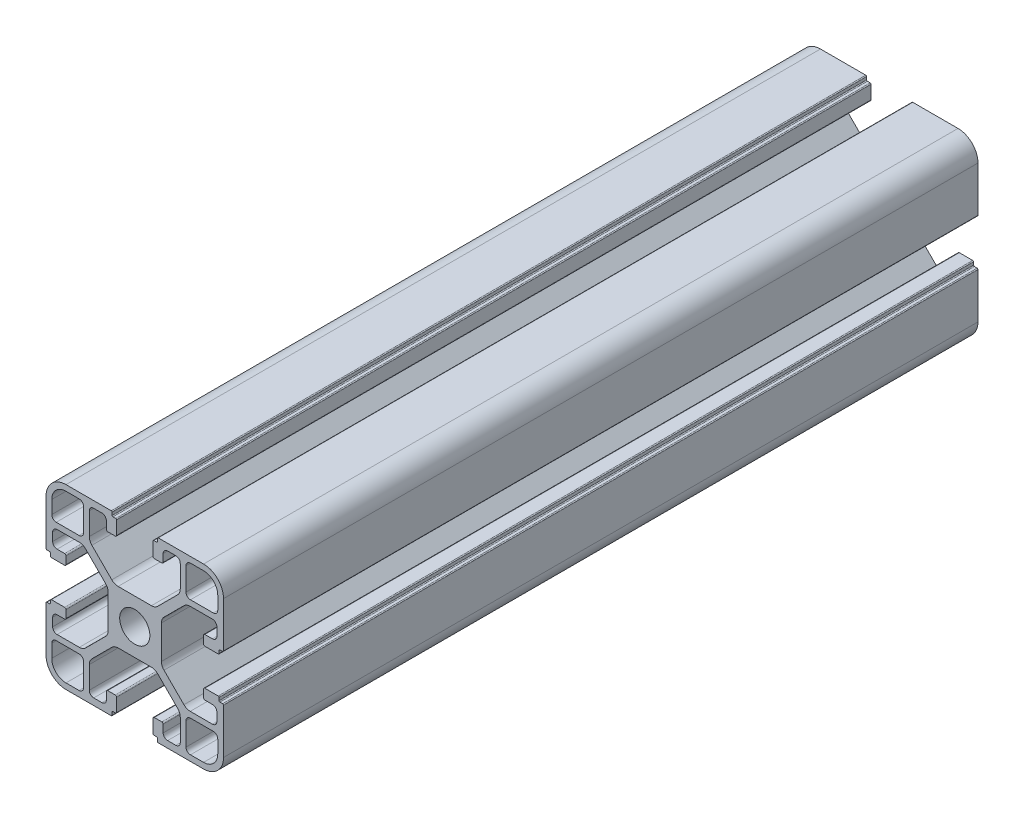
SolidWorks part; units mm, degrees
material "6063-T5"
ref_plane "Front Plane" through (0, 0, 0) normal (0, 0, 1) x (1, 0, 0)
ref_plane "Top Plane" through (0, 0, 0) normal (0, 1, 0) x (1, 0, 0)
ref_plane "Right Plane" through (0, 0, 0) normal (1, 0, 0) x (0, 0, -1)
sketch "Sketch2" plane through (0, 0, 0) normal (0, 0, 1) x (1, 0, 0)
  line L0 (4.5, 0) -> (14.7, 0)
  line L1 (40, 4.5) -> (40, 14.7)
  line L2 (35.5, 40) -> (25.3, 40)
  line L3 (0, 35.5) -> (0, 25.3)
  line L4 (15.9, 1.2) -> (15.9, 4.2)
  line L5 (24.1, 1.2) -> (24.1, 4.2)
  line L6 (38.8, 24.1) -> (35.8, 24.1)
  line L7 (35.5, 24.4) -> (35.5, 26.1)
  line L8 (14, 23.7574) -> (14, 16.2426)
  line L9 (16.2426, 14) -> (23.7574, 14)
  line L10 (26, 16.2426) -> (26, 23.7574)
  line L11 (13.4142, 14.8284) -> (8.9216, 10.3358)
  line L12 (23.7574, 26) -> (16.2426, 26)
  line L13 (4.5, 24.4) -> (4.5, 26.1)
  line L14 (1.2, 24.1) -> (4.2, 24.1)
  line L15 (15.9, 38.8) -> (15.9, 35.8)
  line L16 (14.8284, 26.5858) -> (10.3358, 31.0784)
  line L17 (13.4142, 25.1716) -> (8.9216, 29.6642)
  line L18 (14.8284, 13.4142) -> (10.3358, 8.9216)
  line L19 (25.1716, 13.4142) -> (29.6642, 8.9216)
  line L20 (26.5858, 14.8284) -> (31.0784, 10.3358)
  line L21 (26.5858, 25.1716) -> (31.0784, 29.6642)
  line L22 (25.1716, 26.5858) -> (29.6642, 31.0784)
  line L23 (24.1, 38.8) -> (24.1, 35.8)
  line L24 (14.7, 40) -> (4.5, 40)
  line L25 (25.3, 0) -> (35.5, 0)
  line L26 (38.8, 15.9) -> (35.8, 15.9)
  line L27 (40, 25.3) -> (40, 35.5)
  line L28 (1.2, 15.9) -> (4.2, 15.9)
  line L29 (0, 14.7) -> (0, 4.5)
  line L30 (4.5, 15.6) -> (4.5, 13.9)
  line L31 (35.5, 15.6) -> (35.5, 13.9)
  line L32 (15.6, 35.5) -> (13.9, 35.5)
  line L33 (24.4, 35.5) -> (26.1, 35.5)
  line L34 (15.6, 4.5) -> (13.9, 4.5)
  line L35 (24.4, 4.5) -> (26.1, 4.5)
  line L36 (12.6, 38.5) -> (10.75, 38.5)
  line L37 (1.5, 12.6) -> (1.5, 10.75)
  line L38 (27.4, 1.5) -> (29.25, 1.5)
  line L39 (38.5, 27.4) -> (38.5, 29.25)
  line L40 (38.5, 10.75) -> (38.5, 12.6)
  line L41 (29.25, 38.5) -> (27.4, 38.5)
  line L42 (1.5, 29.25) -> (1.5, 27.4)
  line L43 (10.75, 1.5) -> (12.6, 1.5)
  line L44 (35.8, 26.4) -> (37.5, 26.4)
  line L45 (35.8, 13.6) -> (37.5, 13.6)
  line L46 (4.2, 26.4) -> (2.5, 26.4)
  line L47 (13.6, 35.8) -> (13.6, 37.5)
  line L48 (26.4, 35.8) -> (26.4, 37.5)
  line L49 (4.2, 13.6) -> (2.5, 13.6)
  line L50 (13.6, 4.2) -> (13.6, 2.5)
  line L51 (26.4, 4.2) -> (26.4, 2.5)
  line L52 (9.75, 7.5074) -> (9.75, 2.5)
  line L53 (30.25, 7.5074) -> (30.25, 2.5)
  line L54 (9.75, 37.5) -> (9.75, 32.4926)
  line L55 (30.25, 37.5) -> (30.25, 32.4926)
  line L56 (32.4926, 30.25) -> (37.5, 30.25)
  line L57 (37.5, 9.75) -> (32.4926, 9.75)
  line L58 (2.5, 30.25) -> (7.5074, 30.25)
  line L59 (2.5, 9.75) -> (7.5074, 9.75)
  line L60 (31.55, 37.7) -> (31.55, 32.55)
  line L61 (32.55, 31.55) -> (37.7, 31.55)
  line L62 (1.3, 35.5) -> (1.3, 32.55)
  line L63 (4.5, 38.7) -> (7.45, 38.7)
  line L64 (32.55, 38.7) -> (35.5, 38.7)
  line L65 (38.7, 35.5) -> (38.7, 32.55)
  line L66 (8.45, 37.7) -> (8.45, 32.55)
  line L67 (2.3, 31.55) -> (7.45, 31.55)
  line L68 (1.3, 7.45) -> (1.3, 4.5)
  line L69 (2.3, 8.45) -> (7.45, 8.45)
  line L70 (8.45, 7.45) -> (8.45, 2.3)
  line L71 (4.5, 1.3) -> (7.45, 1.3)
  line L72 (31.55, 7.45) -> (31.55, 2.3)
  line L73 (32.55, 8.45) -> (37.7, 8.45)
  line L74 (38.7, 7.45) -> (38.7, 4.5)
  line L75 (32.55, 1.3) -> (35.5, 1.3)
  line L77 (14.9, 39.8) -> (14.9, 39.2)
  line L78 (15.1, 39) -> (15.7, 39)
  line L79 (25.1, 39.8) -> (25.1, 39.2)
  line L80 (24.9, 39) -> (24.3, 39)
  line L81 (25.1, 0.2) -> (25.1, 0.8)
  line L82 (24.9, 1) -> (24.3, 1)
  line L83 (14.9, 0.2) -> (14.9, 0.8)
  line L84 (15.1, 1) -> (15.7, 1)
  line L85 (0.2, 25.1) -> (0.8, 25.1)
  line L86 (1, 24.9) -> (1, 24.3)
  line L87 (0.2, 14.9) -> (0.8, 14.9)
  line L88 (1, 15.1) -> (1, 15.7)
  line L89 (39.8, 25.1) -> (39.2, 25.1)
  line L90 (39, 24.9) -> (39, 24.3)
  line L91 (39, 15.7) -> (39, 15.1)
  line L92 (39.2, 14.9) -> (39.8, 14.9)
  circle A0 centre (20, 20) radius 3.4
  arc A1 (1.3, 35.5) -> (4.5, 38.7) centre (4.5, 35.5) cw
  arc A2 (1.3, 4.5) -> (4.5, 1.3) centre (4.5, 4.5) ccw
  arc A3 (38.7, 4.5) -> (35.5, 1.3) centre (35.5, 4.5) cw
  arc A4 (35.5, 38.7) -> (38.7, 35.5) centre (35.5, 35.5) cw
  arc A5 (40, 35.5) -> (35.5, 40) centre (35.5, 35.5) ccw
  arc A6 (35.5, 0) -> (40, 4.5) centre (35.5, 4.5) ccw
  arc A7 (4.5, 0) -> (0, 4.5) centre (4.5, 4.5) cw
  arc A8 (4.5, 40) -> (0, 35.5) centre (4.5, 35.5) ccw
  arc A9 (13.4142, 14.8284) -> (14, 16.2426) centre (12, 16.2426) ccw
  arc A10 (7.5074, 9.75) -> (8.9216, 10.3358) centre (7.5074, 11.75) ccw
  arc A11 (9.75, 7.5074) -> (10.3358, 8.9216) centre (11.75, 7.5074) cw
  arc A12 (30.25, 7.5074) -> (29.6642, 8.9216) centre (28.25, 7.5074) ccw
  arc A13 (14.8284, 13.4142) -> (16.2426, 14) centre (16.2426, 12) cw
  arc A14 (25.1716, 13.4142) -> (23.7574, 14) centre (23.7574, 12) ccw
  arc A15 (32.4926, 9.75) -> (31.0784, 10.3358) centre (32.4926, 11.75) cw
  arc A16 (26.5858, 14.8284) -> (26, 16.2426) centre (28, 16.2426) cw
  arc A17 (32.4926, 30.25) -> (31.0784, 29.6642) centre (32.4926, 28.25) ccw
  arc A18 (26.5858, 25.1716) -> (26, 23.7574) centre (28, 23.7574) ccw
  arc A19 (13.4142, 25.1716) -> (14, 23.7574) centre (12, 23.7574) cw
  arc A20 (7.5074, 30.25) -> (8.9216, 29.6642) centre (7.5074, 28.25) cw
  arc A21 (9.75, 32.4926) -> (10.3358, 31.0784) centre (11.75, 32.4926) ccw
  arc A22 (30.25, 32.4926) -> (29.6642, 31.0784) centre (28.25, 32.4926) cw
  arc A23 (25.1716, 26.5858) -> (23.7574, 26) centre (23.7574, 28) cw
  arc A24 (14.8284, 26.5858) -> (16.2426, 26) centre (16.2426, 28) ccw
  arc A25 (37.7, 8.45) -> (38.7, 7.45) centre (37.7, 7.45) cw
  arc A26 (31.55, 2.3) -> (32.55, 1.3) centre (32.55, 2.3) ccw
  arc A27 (31.55, 7.45) -> (32.55, 8.45) centre (32.55, 7.45) cw
  arc A28 (8.45, 2.3) -> (7.45, 1.3) centre (7.45, 2.3) cw
  arc A29 (1.3, 7.45) -> (2.3, 8.45) centre (2.3, 7.45) cw
  arc A30 (7.45, 8.45) -> (8.45, 7.45) centre (7.45, 7.45) cw
  arc A31 (38.7, 32.55) -> (37.7, 31.55) centre (37.7, 32.55) cw
  arc A32 (31.55, 32.55) -> (32.55, 31.55) centre (32.55, 32.55) ccw
  arc A33 (31.55, 37.7) -> (32.55, 38.7) centre (32.55, 37.7) cw
  arc A34 (7.45, 38.7) -> (8.45, 37.7) centre (7.45, 37.7) cw
  arc A35 (8.45, 32.55) -> (7.45, 31.55) centre (7.45, 32.55) cw
  arc A36 (1.3, 32.55) -> (2.3, 31.55) centre (2.3, 32.55) ccw
  arc A37 (30.25, 2.5) -> (29.25, 1.5) centre (29.25, 2.5) cw
  arc A38 (26.4, 2.5) -> (27.4, 1.5) centre (27.4, 2.5) ccw
  arc A39 (13.6, 2.5) -> (12.6, 1.5) centre (12.6, 2.5) cw
  arc A40 (9.75, 2.5) -> (10.75, 1.5) centre (10.75, 2.5) ccw
  arc A41 (26.4, 37.5) -> (27.4, 38.5) centre (27.4, 37.5) cw
  arc A42 (30.25, 37.5) -> (29.25, 38.5) centre (29.25, 37.5) ccw
  arc A43 (37.5, 26.4) -> (38.5, 27.4) centre (37.5, 27.4) ccw
  arc A44 (37.5, 30.25) -> (38.5, 29.25) centre (37.5, 29.25) cw
  arc A45 (37.5, 13.6) -> (38.5, 12.6) centre (37.5, 12.6) cw
  arc A46 (37.5, 9.75) -> (38.5, 10.75) centre (37.5, 10.75) ccw
  arc A47 (2.5, 9.75) -> (1.5, 10.75) centre (2.5, 10.75) cw
  arc A48 (2.5, 13.6) -> (1.5, 12.6) centre (2.5, 12.6) ccw
  arc A49 (2.5, 26.4) -> (1.5, 27.4) centre (2.5, 27.4) cw
  arc A50 (2.5, 30.25) -> (1.5, 29.25) centre (2.5, 29.25) ccw
  arc A51 (9.75, 37.5) -> (10.75, 38.5) centre (10.75, 37.5) cw
  arc A52 (13.6, 37.5) -> (12.6, 38.5) centre (12.6, 37.5) ccw
  arc A53 (26.1, 35.5) -> (26.4, 35.8) centre (26.1, 35.8) ccw
  arc A54 (24.1, 35.8) -> (24.4, 35.5) centre (24.4, 35.8) ccw
  arc A55 (15.9, 35.8) -> (15.6, 35.5) centre (15.6, 35.8) cw
  arc A56 (13.9, 35.5) -> (13.6, 35.8) centre (13.9, 35.8) cw
  arc A57 (13.9, 4.5) -> (13.6, 4.2) centre (13.9, 4.2) ccw
  arc A58 (15.9, 4.2) -> (15.6, 4.5) centre (15.6, 4.2) ccw
  arc A59 (24.1, 4.2) -> (24.4, 4.5) centre (24.4, 4.2) cw
  arc A60 (26.1, 4.5) -> (26.4, 4.2) centre (26.1, 4.2) cw
  arc A61 (35.5, 13.9) -> (35.8, 13.6) centre (35.8, 13.9) ccw
  arc A62 (35.8, 15.9) -> (35.5, 15.6) centre (35.8, 15.6) ccw
  arc A63 (35.8, 24.1) -> (35.5, 24.4) centre (35.8, 24.4) cw
  arc A64 (35.5, 26.1) -> (35.8, 26.4) centre (35.8, 26.1) cw
  arc A65 (4.5, 13.9) -> (4.2, 13.6) centre (4.2, 13.9) cw
  arc A66 (4.2, 15.9) -> (4.5, 15.6) centre (4.2, 15.6) cw
  arc A67 (4.2, 24.1) -> (4.5, 24.4) centre (4.2, 24.4) ccw
  arc A68 (4.5, 26.1) -> (4.2, 26.4) centre (4.2, 26.1) ccw
  arc A69 (25.3, 0) -> (25.1, 0.2) centre (25.3, 0.2) cw
  arc A70 (25.1, 0.8) -> (24.9, 1) centre (24.9, 0.8) ccw
  arc A71 (24.3, 1) -> (24.1, 1.2) centre (24.3, 1.2) cw
  arc A72 (14.7, 0) -> (14.9, 0.2) centre (14.7, 0.2) ccw
  arc A73 (14.9, 0.8) -> (15.1, 1) centre (15.1, 0.8) cw
  arc A74 (15.7, 1) -> (15.9, 1.2) centre (15.7, 1.2) ccw
  arc A75 (39.8, 14.9) -> (40, 14.7) centre (39.8, 14.7) cw
  arc A76 (39, 15.1) -> (39.2, 14.9) centre (39.2, 15.1) ccw
  arc A77 (38.8, 15.9) -> (39, 15.7) centre (38.8, 15.7) cw
  arc A78 (0, 25.3) -> (0.2, 25.1) centre (0.2, 25.3) ccw
  arc A79 (0.8, 25.1) -> (1, 24.9) centre (0.8, 24.9) cw
  arc A80 (1, 24.3) -> (1.2, 24.1) centre (1.2, 24.3) ccw
  arc A81 (0, 14.7) -> (0.2, 14.9) centre (0.2, 14.7) cw
  arc A82 (0.8, 14.9) -> (1, 15.1) centre (0.8, 15.1) ccw
  arc A83 (1, 15.7) -> (1.2, 15.9) centre (1.2, 15.7) cw
  arc A84 (39, 24.3) -> (38.8, 24.1) centre (38.8, 24.3) cw
  arc A85 (39.2, 25.1) -> (39, 24.9) centre (39.2, 24.9) ccw
  arc A86 (40, 25.3) -> (39.8, 25.1) centre (39.8, 25.3) cw
  arc A87 (24.3, 39) -> (24.1, 38.8) centre (24.3, 38.8) ccw
  arc A88 (25.1, 39.2) -> (24.9, 39) centre (24.9, 39.2) cw
  arc A89 (25.3, 40) -> (25.1, 39.8) centre (25.3, 39.8) ccw
  arc A90 (14.9, 39.2) -> (15.1, 39) centre (15.1, 39.2) ccw
  arc A91 (15.7, 39) -> (15.9, 38.8) centre (15.7, 38.8) cw
  arc A92 (14.7, 40) -> (14.9, 39.8) centre (14.7, 39.8) cw
  point P93 (0, 0)
extrude "Boss-Extrude1" add sketch "Sketch2" along normal blind 170
sketch "Sketch3" plane through (0, 0, 170) normal (0, 0, 1) x (1, 0, 0)
  line L76 (25.3, 0) -> (35.5, 0)
  line L77 (40, 4.5) -> (40, 14.7)
  line L78 (39.8, 14.9) -> (39.2, 14.9)
  line L79 (39, 15.1) -> (39, 15.7)
  line L80 (38.8, 15.9) -> (35.8, 15.9)
  line L81 (35.5, 15.6) -> (35.5, 13.9)
  line L82 (35.8, 13.6) -> (37.5, 13.6)
  line L83 (38.5, 12.6) -> (38.5, 10.75)
  line L84 (37.5, 9.75) -> (32.4926, 9.75)
  line L85 (31.0784, 10.3358) -> (26.5858, 14.8284)
  line L86 (26, 16.2426) -> (26, 23.7574)
  line L87 (26.5858, 25.1716) -> (31.0784, 29.6642)
  line L88 (32.4926, 30.25) -> (37.5, 30.25)
  line L89 (38.5, 29.25) -> (38.5, 27.4)
  line L90 (37.5, 26.4) -> (35.8, 26.4)
  line L91 (35.5, 26.1) -> (35.5, 24.4)
  line L92 (35.8, 24.1) -> (38.8, 24.1)
  line L93 (39, 24.3) -> (39, 24.9)
  line L94 (39.2, 25.1) -> (39.8, 25.1)
  line L95 (40, 25.3) -> (40, 35.5)
  line L96 (35.5, 40) -> (25.3, 40)
  line L97 (25.1, 39.8) -> (25.1, 39.2)
  line L98 (24.9, 39) -> (24.3, 39)
  line L99 (24.1, 38.8) -> (24.1, 35.8)
  line L100 (24.4, 35.5) -> (26.1, 35.5)
  line L101 (26.4, 35.8) -> (26.4, 37.5)
  line L102 (27.4, 38.5) -> (29.25, 38.5)
  line L103 (30.25, 37.5) -> (30.25, 32.4926)
  line L104 (29.6642, 31.0784) -> (25.1716, 26.5858)
  line L105 (23.7574, 26) -> (16.2426, 26)
  line L106 (14.8284, 26.5858) -> (10.3358, 31.0784)
  line L107 (9.75, 32.4926) -> (9.75, 37.5)
  line L108 (10.75, 38.5) -> (12.6, 38.5)
  line L109 (13.6, 37.5) -> (13.6, 35.8)
  line L110 (13.9, 35.5) -> (15.6, 35.5)
  line L111 (15.9, 35.8) -> (15.9, 38.8)
  line L112 (15.7, 39) -> (15.1, 39)
  line L113 (14.9, 39.2) -> (14.9, 39.8)
  line L114 (14.7, 40) -> (4.5, 40)
  line L115 (0, 35.5) -> (0, 25.3)
  line L116 (0.2, 25.1) -> (0.8, 25.1)
  line L117 (1, 24.9) -> (1, 24.3)
  line L118 (1.2, 24.1) -> (4.2, 24.1)
  line L119 (4.5, 24.4) -> (4.5, 26.1)
  line L120 (4.2, 26.4) -> (2.5, 26.4)
  line L121 (1.5, 27.4) -> (1.5, 29.25)
  line L122 (2.5, 30.25) -> (7.5074, 30.25)
  line L123 (8.9216, 29.6642) -> (13.4142, 25.1716)
  line L124 (14, 23.7574) -> (14, 16.2426)
  line L125 (13.4142, 14.8284) -> (8.9216, 10.3358)
  line L126 (7.5074, 9.75) -> (2.5, 9.75)
  line L127 (1.5, 10.75) -> (1.5, 12.6)
  line L128 (2.5, 13.6) -> (4.2, 13.6)
  line L129 (4.5, 13.9) -> (4.5, 15.6)
  line L130 (4.2, 15.9) -> (1.2, 15.9)
  line L131 (1, 15.7) -> (1, 15.1)
  line L132 (0.8, 14.9) -> (0.2, 14.9)
  line L133 (0, 14.7) -> (0, 4.5)
  line L134 (4.5, 0) -> (14.7, 0)
  line L135 (14.9, 0.2) -> (14.9, 0.8)
  line L136 (15.1, 1) -> (15.7, 1)
  line L137 (15.9, 1.2) -> (15.9, 4.2)
  line L138 (15.6, 4.5) -> (13.9, 4.5)
  line L139 (13.6, 4.2) -> (13.6, 2.5)
  line L140 (12.6, 1.5) -> (10.75, 1.5)
  line L141 (9.75, 2.5) -> (9.75, 7.5074)
  line L142 (10.3358, 8.9216) -> (14.8284, 13.4142)
  line L143 (16.2426, 14) -> (23.7574, 14)
  line L144 (25.1716, 13.4142) -> (29.6642, 8.9216)
  line L145 (30.25, 7.5074) -> (30.25, 2.5)
  line L146 (29.25, 1.5) -> (27.4, 1.5)
  line L147 (26.4, 2.5) -> (26.4, 4.2)
  line L148 (26.1, 4.5) -> (24.4, 4.5)
  line L149 (24.1, 4.2) -> (24.1, 1.2)
  line L150 (24.3, 1) -> (24.9, 1)
  line L151 (25.1, 0.8) -> (25.1, 0.2)
  line L152 (25.3, 0) -> (35.5, 0)
  line L153 (40, 4.5) -> (40, 14.7)
  line L154 (39.8, 14.9) -> (39.2, 14.9)
  line L155 (39, 15.1) -> (39, 15.7)
  line L156 (38.8, 15.9) -> (35.8, 15.9)
  line L157 (35.5, 15.6) -> (35.5, 13.9)
  line L158 (35.8, 13.6) -> (37.5, 13.6)
  line L159 (38.5, 12.6) -> (38.5, 10.75)
  line L160 (37.5, 9.75) -> (32.4926, 9.75)
  line L161 (31.0784, 10.3358) -> (26.5858, 14.8284)
  line L162 (26, 16.2426) -> (26, 23.7574)
  line L163 (26.5858, 25.1716) -> (31.0784, 29.6642)
  line L164 (32.4926, 30.25) -> (37.5, 30.25)
  line L165 (38.5, 29.25) -> (38.5, 27.4)
  line L166 (37.5, 26.4) -> (35.8, 26.4)
  line L167 (35.5, 26.1) -> (35.5, 24.4)
  line L168 (35.8, 24.1) -> (38.8, 24.1)
  line L169 (39, 24.3) -> (39, 24.9)
  line L170 (39.2, 25.1) -> (39.8, 25.1)
  line L171 (40, 25.3) -> (40, 35.5)
  line L172 (35.5, 40) -> (25.3, 40)
  line L173 (25.1, 39.8) -> (25.1, 39.2)
  line L174 (24.9, 39) -> (24.3, 39)
  line L175 (24.1, 38.8) -> (24.1, 35.8)
  line L176 (24.4, 35.5) -> (26.1, 35.5)
  line L177 (26.4, 35.8) -> (26.4, 37.5)
  line L178 (27.4, 38.5) -> (29.25, 38.5)
  line L179 (30.25, 37.5) -> (30.25, 32.4926)
  line L180 (29.6642, 31.0784) -> (25.1716, 26.5858)
  line L181 (23.7574, 26) -> (16.2426, 26)
  line L182 (14.8284, 26.5858) -> (10.3358, 31.0784)
  line L183 (9.75, 32.4926) -> (9.75, 37.5)
  line L184 (10.75, 38.5) -> (12.6, 38.5)
  line L185 (13.6, 37.5) -> (13.6, 35.8)
  line L186 (13.9, 35.5) -> (15.6, 35.5)
  line L187 (15.9, 35.8) -> (15.9, 38.8)
  line L188 (15.7, 39) -> (15.1, 39)
  line L189 (14.9, 39.2) -> (14.9, 39.8)
  line L190 (14.7, 40) -> (4.5, 40)
  line L191 (0, 35.5) -> (0, 25.3)
  line L192 (0.2, 25.1) -> (0.8, 25.1)
  line L193 (1, 24.9) -> (1, 24.3)
  line L194 (1.2, 24.1) -> (4.2, 24.1)
  line L195 (4.5, 24.4) -> (4.5, 26.1)
  line L196 (4.2, 26.4) -> (2.5, 26.4)
  line L197 (1.5, 27.4) -> (1.5, 29.25)
  line L198 (2.5, 30.25) -> (7.5074, 30.25)
  line L199 (8.9216, 29.6642) -> (13.4142, 25.1716)
  line L200 (14, 23.7574) -> (14, 16.2426)
  line L201 (13.4142, 14.8284) -> (8.9216, 10.3358)
  line L202 (7.5074, 9.75) -> (2.5, 9.75)
  line L203 (1.5, 10.75) -> (1.5, 12.6)
  line L204 (2.5, 13.6) -> (4.2, 13.6)
  line L205 (4.5, 13.9) -> (4.5, 15.6)
  line L206 (4.2, 15.9) -> (1.2, 15.9)
  line L207 (1, 15.7) -> (1, 15.1)
  line L208 (0.8, 14.9) -> (0.2, 14.9)
  line L209 (0, 14.7) -> (0, 4.5)
  line L210 (4.5, 0) -> (14.7, 0)
  line L211 (14.9, 0.2) -> (14.9, 0.8)
  line L212 (15.1, 1) -> (15.7, 1)
  line L213 (15.9, 1.2) -> (15.9, 4.2)
  line L214 (15.6, 4.5) -> (13.9, 4.5)
  line L215 (13.6, 4.2) -> (13.6, 2.5)
  line L216 (12.6, 1.5) -> (10.75, 1.5)
  line L217 (9.75, 2.5) -> (9.75, 7.5074)
  line L218 (10.3358, 8.9216) -> (14.8284, 13.4142)
  line L219 (16.2426, 14) -> (23.7574, 14)
  line L220 (25.1716, 13.4142) -> (29.6642, 8.9216)
  line L221 (30.25, 7.5074) -> (30.25, 2.5)
  line L222 (29.25, 1.5) -> (27.4, 1.5)
  line L223 (26.4, 2.5) -> (26.4, 4.2)
  line L224 (26.1, 4.5) -> (24.4, 4.5)
  line L225 (24.1, 4.2) -> (24.1, 1.2)
  line L226 (24.3, 1) -> (24.9, 1)
  line L227 (25.1, 0.8) -> (25.1, 0.2)
  arc A76 (25.1, 0.2) -> (25.3, 0) centre (25.3, 0.2) ccw
  arc A77 (35.5, 0) -> (40, 4.5) centre (35.5, 4.5) ccw
  arc A78 (40, 14.7) -> (39.8, 14.9) centre (39.8, 14.7) ccw
  arc A79 (39, 15.1) -> (39.2, 14.9) centre (39.2, 15.1) ccw
  arc A80 (39, 15.7) -> (38.8, 15.9) centre (38.8, 15.7) ccw
  arc A81 (35.8, 15.9) -> (35.5, 15.6) centre (35.8, 15.6) ccw
  arc A82 (35.5, 13.9) -> (35.8, 13.6) centre (35.8, 13.9) ccw
  arc A83 (38.5, 12.6) -> (37.5, 13.6) centre (37.5, 12.6) ccw
  arc A84 (37.5, 9.75) -> (38.5, 10.75) centre (37.5, 10.75) ccw
  arc A85 (31.0784, 10.3358) -> (32.4926, 9.75) centre (32.4926, 11.75) ccw
  arc A86 (26, 16.2426) -> (26.5858, 14.8284) centre (28, 16.2426) ccw
  arc A87 (26.5858, 25.1716) -> (26, 23.7574) centre (28, 23.7574) ccw
  arc A88 (32.4926, 30.25) -> (31.0784, 29.6642) centre (32.4926, 28.25) ccw
  arc A89 (38.5, 29.25) -> (37.5, 30.25) centre (37.5, 29.25) ccw
  arc A90 (37.5, 26.4) -> (38.5, 27.4) centre (37.5, 27.4) ccw
  arc A91 (35.8, 26.4) -> (35.5, 26.1) centre (35.8, 26.1) ccw
  arc A92 (35.5, 24.4) -> (35.8, 24.1) centre (35.8, 24.4) ccw
  arc A93 (38.8, 24.1) -> (39, 24.3) centre (38.8, 24.3) ccw
  arc A94 (39.2, 25.1) -> (39, 24.9) centre (39.2, 24.9) ccw
  arc A95 (39.8, 25.1) -> (40, 25.3) centre (39.8, 25.3) ccw
  arc A96 (40, 35.5) -> (35.5, 40) centre (35.5, 35.5) ccw
  arc A97 (25.3, 40) -> (25.1, 39.8) centre (25.3, 39.8) ccw
  arc A98 (24.9, 39) -> (25.1, 39.2) centre (24.9, 39.2) ccw
  arc A99 (24.3, 39) -> (24.1, 38.8) centre (24.3, 38.8) ccw
  arc A100 (24.1, 35.8) -> (24.4, 35.5) centre (24.4, 35.8) ccw
  arc A101 (26.1, 35.5) -> (26.4, 35.8) centre (26.1, 35.8) ccw
  arc A102 (27.4, 38.5) -> (26.4, 37.5) centre (27.4, 37.5) ccw
  arc A103 (30.25, 37.5) -> (29.25, 38.5) centre (29.25, 37.5) ccw
  arc A104 (29.6642, 31.0784) -> (30.25, 32.4926) centre (28.25, 32.4926) ccw
  arc A105 (23.7574, 26) -> (25.1716, 26.5858) centre (23.7574, 28) ccw
  arc A106 (14.8284, 26.5858) -> (16.2426, 26) centre (16.2426, 28) ccw
  arc A107 (9.75, 32.4926) -> (10.3358, 31.0784) centre (11.75, 32.4926) ccw
  arc A108 (10.75, 38.5) -> (9.75, 37.5) centre (10.75, 37.5) ccw
  arc A109 (13.6, 37.5) -> (12.6, 38.5) centre (12.6, 37.5) ccw
  arc A110 (13.6, 35.8) -> (13.9, 35.5) centre (13.9, 35.8) ccw
  arc A111 (15.6, 35.5) -> (15.9, 35.8) centre (15.6, 35.8) ccw
  arc A112 (15.9, 38.8) -> (15.7, 39) centre (15.7, 38.8) ccw
  arc A113 (14.9, 39.2) -> (15.1, 39) centre (15.1, 39.2) ccw
  arc A114 (14.9, 39.8) -> (14.7, 40) centre (14.7, 39.8) ccw
  arc A115 (4.5, 40) -> (0, 35.5) centre (4.5, 35.5) ccw
  arc A116 (0, 25.3) -> (0.2, 25.1) centre (0.2, 25.3) ccw
  arc A117 (1, 24.9) -> (0.8, 25.1) centre (0.8, 24.9) ccw
  arc A118 (1, 24.3) -> (1.2, 24.1) centre (1.2, 24.3) ccw
  arc A119 (4.2, 24.1) -> (4.5, 24.4) centre (4.2, 24.4) ccw
  arc A120 (4.5, 26.1) -> (4.2, 26.4) centre (4.2, 26.1) ccw
  arc A121 (1.5, 27.4) -> (2.5, 26.4) centre (2.5, 27.4) ccw
  arc A122 (2.5, 30.25) -> (1.5, 29.25) centre (2.5, 29.25) ccw
  arc A123 (8.9216, 29.6642) -> (7.5074, 30.25) centre (7.5074, 28.25) ccw
  arc A124 (14, 23.7574) -> (13.4142, 25.1716) centre (12, 23.7574) ccw
  arc A125 (13.4142, 14.8284) -> (14, 16.2426) centre (12, 16.2426) ccw
  arc A126 (7.5074, 9.75) -> (8.9216, 10.3358) centre (7.5074, 11.75) ccw
  arc A127 (1.5, 10.75) -> (2.5, 9.75) centre (2.5, 10.75) ccw
  arc A128 (2.5, 13.6) -> (1.5, 12.6) centre (2.5, 12.6) ccw
  arc A129 (4.2, 13.6) -> (4.5, 13.9) centre (4.2, 13.9) ccw
  arc A130 (4.5, 15.6) -> (4.2, 15.9) centre (4.2, 15.6) ccw
  arc A131 (1.2, 15.9) -> (1, 15.7) centre (1.2, 15.7) ccw
  arc A132 (0.8, 14.9) -> (1, 15.1) centre (0.8, 15.1) ccw
  arc A133 (0.2, 14.9) -> (0, 14.7) centre (0.2, 14.7) ccw
  arc A134 (0, 4.5) -> (4.5, 0) centre (4.5, 4.5) ccw
  arc A135 (14.7, 0) -> (14.9, 0.2) centre (14.7, 0.2) ccw
  arc A136 (15.1, 1) -> (14.9, 0.8) centre (15.1, 0.8) ccw
  arc A137 (15.7, 1) -> (15.9, 1.2) centre (15.7, 1.2) ccw
  arc A138 (15.9, 4.2) -> (15.6, 4.5) centre (15.6, 4.2) ccw
  arc A139 (13.9, 4.5) -> (13.6, 4.2) centre (13.9, 4.2) ccw
  arc A140 (12.6, 1.5) -> (13.6, 2.5) centre (12.6, 2.5) ccw
  arc A141 (9.75, 2.5) -> (10.75, 1.5) centre (10.75, 2.5) ccw
  arc A142 (10.3358, 8.9216) -> (9.75, 7.5074) centre (11.75, 7.5074) ccw
  arc A143 (16.2426, 14) -> (14.8284, 13.4142) centre (16.2426, 12) ccw
  arc A144 (25.1716, 13.4142) -> (23.7574, 14) centre (23.7574, 12) ccw
  arc A145 (30.25, 7.5074) -> (29.6642, 8.9216) centre (28.25, 7.5074) ccw
  arc A146 (29.25, 1.5) -> (30.25, 2.5) centre (29.25, 2.5) ccw
  arc A147 (26.4, 2.5) -> (27.4, 1.5) centre (27.4, 2.5) ccw
  arc A148 (26.4, 4.2) -> (26.1, 4.5) centre (26.1, 4.2) ccw
  arc A149 (24.4, 4.5) -> (24.1, 4.2) centre (24.4, 4.2) ccw
  arc A150 (24.1, 1.2) -> (24.3, 1) centre (24.3, 1.2) ccw
  arc A151 (25.1, 0.8) -> (24.9, 1) centre (24.9, 0.8) ccw
  arc A152 (25.1, 0.2) -> (25.3, 0) centre (25.3, 0.2) ccw
  arc A153 (35.5, 0) -> (40, 4.5) centre (35.5, 4.5) ccw
  arc A154 (40, 14.7) -> (39.8, 14.9) centre (39.8, 14.7) ccw
  arc A155 (39, 15.1) -> (39.2, 14.9) centre (39.2, 15.1) ccw
  arc A156 (39, 15.7) -> (38.8, 15.9) centre (38.8, 15.7) ccw
  arc A157 (35.8, 15.9) -> (35.5, 15.6) centre (35.8, 15.6) ccw
  arc A158 (35.5, 13.9) -> (35.8, 13.6) centre (35.8, 13.9) ccw
  arc A159 (38.5, 12.6) -> (37.5, 13.6) centre (37.5, 12.6) ccw
  arc A160 (37.5, 9.75) -> (38.5, 10.75) centre (37.5, 10.75) ccw
  arc A161 (31.0784, 10.3358) -> (32.4926, 9.75) centre (32.4926, 11.75) ccw
  arc A162 (26, 16.2426) -> (26.5858, 14.8284) centre (28, 16.2426) ccw
  arc A163 (26.5858, 25.1716) -> (26, 23.7574) centre (28, 23.7574) ccw
  arc A164 (32.4926, 30.25) -> (31.0784, 29.6642) centre (32.4926, 28.25) ccw
  arc A165 (38.5, 29.25) -> (37.5, 30.25) centre (37.5, 29.25) ccw
  arc A166 (37.5, 26.4) -> (38.5, 27.4) centre (37.5, 27.4) ccw
  arc A167 (35.8, 26.4) -> (35.5, 26.1) centre (35.8, 26.1) ccw
  arc A168 (35.5, 24.4) -> (35.8, 24.1) centre (35.8, 24.4) ccw
  arc A169 (38.8, 24.1) -> (39, 24.3) centre (38.8, 24.3) ccw
  arc A170 (39.2, 25.1) -> (39, 24.9) centre (39.2, 24.9) ccw
  arc A171 (39.8, 25.1) -> (40, 25.3) centre (39.8, 25.3) ccw
  arc A172 (40, 35.5) -> (35.5, 40) centre (35.5, 35.5) ccw
  arc A173 (25.3, 40) -> (25.1, 39.8) centre (25.3, 39.8) ccw
  arc A174 (24.9, 39) -> (25.1, 39.2) centre (24.9, 39.2) ccw
  arc A175 (24.3, 39) -> (24.1, 38.8) centre (24.3, 38.8) ccw
  arc A176 (24.1, 35.8) -> (24.4, 35.5) centre (24.4, 35.8) ccw
  arc A177 (26.1, 35.5) -> (26.4, 35.8) centre (26.1, 35.8) ccw
  arc A178 (27.4, 38.5) -> (26.4, 37.5) centre (27.4, 37.5) ccw
  arc A179 (30.25, 37.5) -> (29.25, 38.5) centre (29.25, 37.5) ccw
  arc A180 (29.6642, 31.0784) -> (30.25, 32.4926) centre (28.25, 32.4926) ccw
  arc A181 (23.7574, 26) -> (25.1716, 26.5858) centre (23.7574, 28) ccw
  arc A182 (14.8284, 26.5858) -> (16.2426, 26) centre (16.2426, 28) ccw
  arc A183 (9.75, 32.4926) -> (10.3358, 31.0784) centre (11.75, 32.4926) ccw
  arc A184 (10.75, 38.5) -> (9.75, 37.5) centre (10.75, 37.5) ccw
  arc A185 (13.6, 37.5) -> (12.6, 38.5) centre (12.6, 37.5) ccw
  arc A186 (13.6, 35.8) -> (13.9, 35.5) centre (13.9, 35.8) ccw
  arc A187 (15.6, 35.5) -> (15.9, 35.8) centre (15.6, 35.8) ccw
  arc A188 (15.9, 38.8) -> (15.7, 39) centre (15.7, 38.8) ccw
  arc A189 (14.9, 39.2) -> (15.1, 39) centre (15.1, 39.2) ccw
  arc A190 (14.9, 39.8) -> (14.7, 40) centre (14.7, 39.8) ccw
  arc A191 (4.5, 40) -> (0, 35.5) centre (4.5, 35.5) ccw
  arc A192 (0, 25.3) -> (0.2, 25.1) centre (0.2, 25.3) ccw
  arc A193 (1, 24.9) -> (0.8, 25.1) centre (0.8, 24.9) ccw
  arc A194 (1, 24.3) -> (1.2, 24.1) centre (1.2, 24.3) ccw
  arc A195 (4.2, 24.1) -> (4.5, 24.4) centre (4.2, 24.4) ccw
  arc A196 (4.5, 26.1) -> (4.2, 26.4) centre (4.2, 26.1) ccw
  arc A197 (1.5, 27.4) -> (2.5, 26.4) centre (2.5, 27.4) ccw
  arc A198 (2.5, 30.25) -> (1.5, 29.25) centre (2.5, 29.25) ccw
  arc A199 (8.9216, 29.6642) -> (7.5074, 30.25) centre (7.5074, 28.25) ccw
  arc A200 (14, 23.7574) -> (13.4142, 25.1716) centre (12, 23.7574) ccw
  arc A201 (13.4142, 14.8284) -> (14, 16.2426) centre (12, 16.2426) ccw
  arc A202 (7.5074, 9.75) -> (8.9216, 10.3358) centre (7.5074, 11.75) ccw
  arc A203 (1.5, 10.75) -> (2.5, 9.75) centre (2.5, 10.75) ccw
  arc A204 (2.5, 13.6) -> (1.5, 12.6) centre (2.5, 12.6) ccw
  arc A205 (4.2, 13.6) -> (4.5, 13.9) centre (4.2, 13.9) ccw
  arc A206 (4.5, 15.6) -> (4.2, 15.9) centre (4.2, 15.6) ccw
  arc A207 (1.2, 15.9) -> (1, 15.7) centre (1.2, 15.7) ccw
  arc A208 (0.8, 14.9) -> (1, 15.1) centre (0.8, 15.1) ccw
  arc A209 (0.2, 14.9) -> (0, 14.7) centre (0.2, 14.7) ccw
  arc A210 (0, 4.5) -> (4.5, 0) centre (4.5, 4.5) ccw
  arc A211 (14.7, 0) -> (14.9, 0.2) centre (14.7, 0.2) ccw
  arc A212 (15.1, 1) -> (14.9, 0.8) centre (15.1, 0.8) ccw
  arc A213 (15.7, 1) -> (15.9, 1.2) centre (15.7, 1.2) ccw
  arc A214 (15.9, 4.2) -> (15.6, 4.5) centre (15.6, 4.2) ccw
  arc A215 (13.9, 4.5) -> (13.6, 4.2) centre (13.9, 4.2) ccw
  arc A216 (12.6, 1.5) -> (13.6, 2.5) centre (12.6, 2.5) ccw
  arc A217 (9.75, 2.5) -> (10.75, 1.5) centre (10.75, 2.5) ccw
  arc A218 (10.3358, 8.9216) -> (9.75, 7.5074) centre (11.75, 7.5074) ccw
  arc A219 (16.2426, 14) -> (14.8284, 13.4142) centre (16.2426, 12) ccw
  arc A220 (25.1716, 13.4142) -> (23.7574, 14) centre (23.7574, 12) ccw
  arc A221 (30.25, 7.5074) -> (29.6642, 8.9216) centre (28.25, 7.5074) ccw
  arc A222 (29.25, 1.5) -> (30.25, 2.5) centre (29.25, 2.5) ccw
  arc A223 (26.4, 2.5) -> (27.4, 1.5) centre (27.4, 2.5) ccw
  arc A224 (26.4, 4.2) -> (26.1, 4.5) centre (26.1, 4.2) ccw
  arc A225 (24.4, 4.5) -> (24.1, 4.2) centre (24.4, 4.2) ccw
  arc A226 (24.1, 1.2) -> (24.3, 1) centre (24.3, 1.2) ccw
  arc A227 (25.1, 0.8) -> (24.9, 1) centre (24.9, 0.8) ccw
  dimension "D1" = 0
sketch "Sketch4" plane through (0, 0, 0) normal (-1, 0, 0) x (0, 0, 1)
  line L0 (15, 20) -> (68, 20) construction
  line L2 (0, 23.7574) -> (0, 16.2426) construction
  circle A0 centre (15, 20) radius 2.5
  circle A1 centre (68, 20) radius 2.5
  dimension "D1" = 5
  dimension "D2" = 53
  dimension "D3" = 15
extrude "Cut-Extrude1" cut sketch "Sketch4" against normal through all contours A1 | A0 region at (0, 20, 68)
